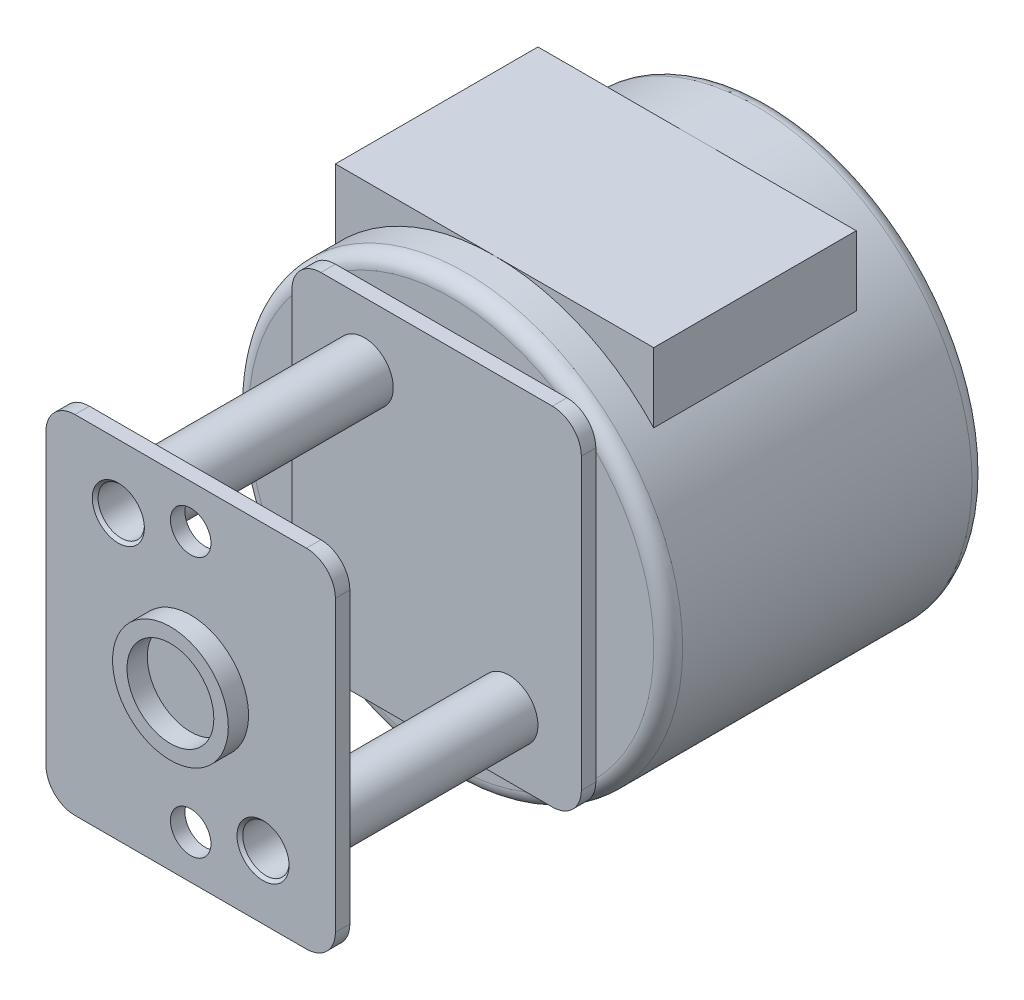
SolidWorks part; units mm, degrees
material "Vanadium"
ref_plane "Front Plane" through (0, 0, 0) normal (0, 0, 1) x (1, 0, 0)
ref_plane "Top Plane" through (0, 0, 0) normal (0, 1, 0) x (1, 0, 0)
ref_plane "Right Plane" through (0, 0, 0) normal (1, 0, 0) x (0, 0, -1)
sketch "Sketch1" plane through (0, 0, 0) normal (0, 0, 1) x (1, 0, 0)
  circle A0 centre (0, 0) radius 7.5
  dimension "D1" = 15
extrude "Boss-Extrude1" add sketch "Sketch1" along normal blind 11
fillet "Fillet1" radius 0.5 2 edges at (7.5, 0, 0) (7.5, 0, 11)
sketch "Sketch2" plane through (0, 0, 11) normal (0, 0, 1) x (1, 0, 0)
  line L1 (-4, 6) -> (4, 6)
  line L2 (-5, 5) -> (-5, -5)
  line L3 (-4, -6) -> (4, -6)
  line L4 (5, 5) -> (5, -5)
  line L5 (-5, 6) -> (5, -6) construction
  line L6 (-5, -6) -> (5, 6) construction
  arc A0 (-5, -5) -> (-4, -6) centre (-4, -5) ccw
  arc A1 (4, -6) -> (5, -5) centre (4, -5) ccw
  arc A2 (4, 6) -> (5, 5) centre (4, 5) cw
  arc A3 (-4, 6) -> (-5, 5) centre (-4, 5) ccw
  point P0 (0, 0)
  dimension "D3" = 1
  dimension "D1" = 12
  dimension "D2" = 10
extrude "Boss-Extrude2" add sketch "Sketch2" along normal blind 9
ref_plane "Plane1" through (0, 0, 15.5) normal (0, 0, 1) x (1, 0, 0)
sketch "Sketch3" plane through (0, 0, 15.5) normal (0, 0, 1) x (1, 0, 0)
  line L80 (-10, 10) -> (10, 10)
  line L81 (-10, 10) -> (-10, -10)
  line L82 (-10, -10) -> (10, -10)
  line L83 (10, 10) -> (10, -10)
  line L84 (-10, 10) -> (10, -10) construction
  line L85 (-10, -10) -> (10, 10) construction
  point P16 (0, 0)
  dimension "D1" = 20
  dimension "D2" = 20
extrude "Cut-Extrude4" cut sketch "Sketch3" against normal mid plane 8
sketch "Sketch5" plane through (0, 0, 11.5) normal (0, 0, 1) x (1, 0, 0)
  line L0 (0, -3.8) -> (2.5, -3.8) construction
  line L1 (-2.5, 3.8) -> (0, 3.8) construction
  circle A0 centre (-2.5, 3.8) radius 1
  circle A1 centre (2.5, -3.8) radius 1
  circle A2 centre (0, 4.5) radius 0.7
  circle A3 centre (0, -4.5) radius 0.7
  circle A4 centre (-2.5, 3.8) radius 0.8
  circle A5 centre (2.5, -3.8) radius 0.8
  dimension "D1" = 2
  dimension "D2" = 1.4
  dimension "D3" = 9
  dimension "D4" = 4.5
  dimension "D5" = 2.5
  dimension "D6" = 0.2
extrude "Boss-Extrude3" add sketch "Sketch5" along normal up to surface (8 mm away) contours A0 | A1 up to face at (0, 0, 19.5)
extrude "Cut-Extrude5" cut sketch "Sketch5<3>" along normal blind 10 contours A2 | A3
sketch "Sketch5<3>" plane through (0, 0, 11.5) normal (0, 0, 1) x (1, 0, 0) same geometry as "Sketch5"
extrude "Cut-Extrude6" cut sketch "Sketch5<4>" along normal up to surface (8.5 mm away) contours A4 | A5 up to face at (0.7, 4.5, 20)
sketch "Sketch5<4>" plane through (0, 0, 11.5) normal (0, 0, 1) x (1, 0, 0) same geometry as "Sketch5"
sketch "Sketch6" plane through (0, 0, 20) normal (0, 0, 1) x (1, 0, 0)
  circle A0 centre (0, 0) radius 2
  circle A1 centre (0, 0) radius 1.5
  dimension "D1" = 4
  dimension "D2" = 3
extrude "Boss-Extrude4" add sketch "Sketch6" along normal blind 0.7
chamfer "Chamfer1" distance 0.1 angle 45 2 edges at (3.3, -3.8, 20) (-1.7, 3.8, 20)
ref_plane "Plane2" through (0, 7.5, 0) normal (0, 1, 0) x (1, 0, 0)
sketch "Sketch9" plane through (0, 7.5, 0) normal (0, 1, 0) x (1, 0, 0)
  line L0 (7.5, -10.5) -> (-7.5, -10.5) construction
  line L1 (-5.5, -2.5) -> (5.5, -2.5)
  line L2 (-5.5, -2.5) -> (-5.5, -9.5)
  line L3 (-5.5, -9.5) -> (5.5, -9.5)
  line L4 (5.5, -2.5) -> (5.5, -9.5)
  line L5 (-5.5, -2.5) -> (5.5, -9.5) construction
  line L6 (-5.5, -9.5) -> (5.5, -2.5) construction
  point P0 (0, -6)
  dimension "D1" = 7
  dimension "D2" = 11
  dimension "D3" = 1
extrude "Boss-Extrude6" add sketch "Sketch9" against normal blind 3
